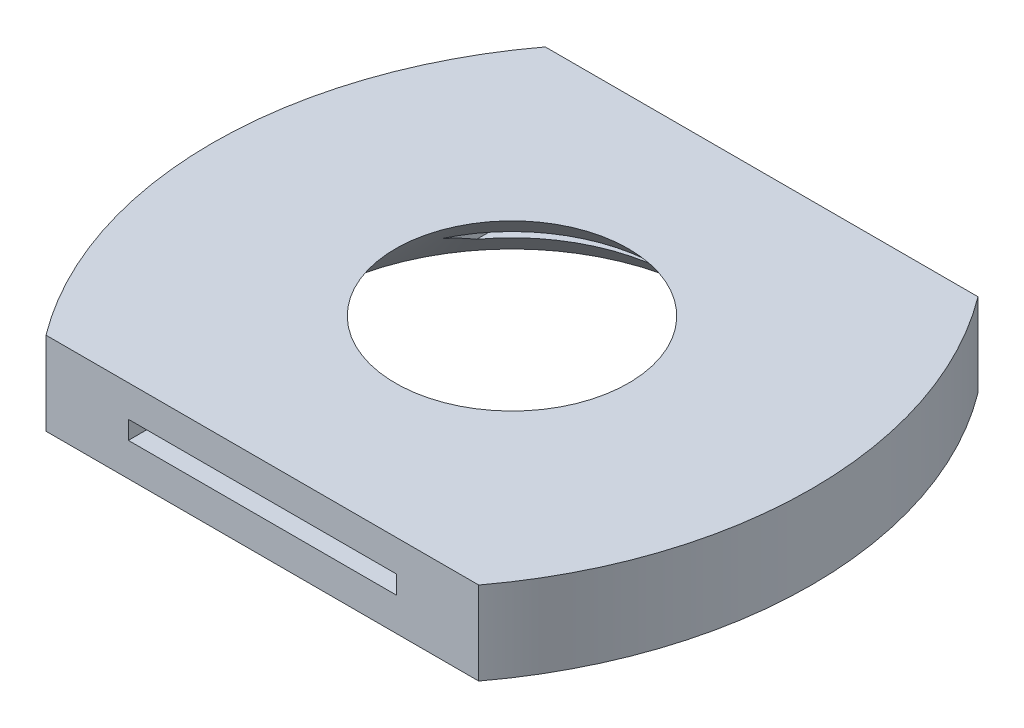
SolidWorks part; units mm, degrees
ref_plane "Front Plane" through (0, 0, 0) normal (0, 0, 1) x (1, 0, 0)
ref_plane "Top Plane" through (0, 0, 0) normal (0, 1, 0) x (1, 0, 0)
ref_plane "Right Plane" through (0, 0, 0) normal (1, 0, 0) x (0, 0, -1)
sketch "Lid case" plane through (0, 0, 0) normal (0, 1, 0) x (1, 0, 0)
  line L0 (-130, 150) -> (130, 150)
  line L1 (-130, -150) -> (130, -150)
  arc A0 (130, 150) -> (130, -150) centre (-70, 0) cw
  arc A1 (-130, 150) -> (-130, -150) centre (70, 0) ccw
  dimension "D6" = 250
  dimension "D7" = 250
  dimension "D1" = 260
  dimension "D2" = 130
  dimension "D3" = 150
  dimension "D4" = 150
  dimension "D5" = 130
extrude "Boss-Extrude1" add sketch "Lid case" along normal blind 50
ref_axis "Axis1" through (0, -54.3732, 0) along (0, 1, 0)
ref_plane "Plane1" through (0, 0, 0) normal (0, 0, 1) x (1, 0, 0)
sketch "Ventilation" plane through (0, 0, 0) normal (0, 0, 1) x (1, 0, 0)
  line L0 (0, 50) -> (0, 0)
  line L1 (0, 0) -> (-120, 0)
  line L2 (-120, 0) -> (-70, 50)
  line L4 (0, -54.3732) -> (0, 100.2697) construction
  line L5 (-130, 0) -> (130, 0) construction
  line L6 (-70, 50) -> (0, 50)
  line L7 (-130, 50) -> (130, 50) construction
  dimension "D2" = 120
  dimension "D3" = 45
revolve "Cut-Revolve1" cut sketch "Ventilation" angle 360 about axis through (0, -54.3732, 0) along (0, 1, 0)
sketch "Carbon filter hole" plane through (0, 0, 150) normal (0, 0, 1) x (1, 0, 0)
  line L0 (0, -54.3732) -> (0, 100.2697) construction
  line L1 (-80.5, 31) -> (80.5, 31)
  line L2 (-80.5, 31) -> (-80.5, 20)
  line L3 (-80.5, 20) -> (80.5, 20)
  line L4 (80.5, 31) -> (80.5, 20)
  line L6 (-130, 0) -> (130, 0) construction
  dimension "D1" = 161
  dimension "D2" = 11
  dimension "D3" = 80.5
  dimension "D4" = 20
extrude "Cut-Extrude3" cut sketch "Carbon filter hole" against normal blind 280
sketch "Sketch1" plane through (0, 0, 0) normal (0, -1, 0) x (1, 0, 0)
  line L0 (130, -150) -> (-130, -150) construction
  circle A0 centre (-110, -139) radius 3
  circle A1 centre (-82, -139) radius 3
  circle A2 centre (-54, -139) radius 3
  circle A3 centre (54, -139) radius 3
  circle A4 centre (82, -139) radius 3
  circle A5 centre (110, -139) radius 3
  point P16 (0, 0)
  dimension "D1" = 6
  dimension "D2" = 20
  dimension "D3" = 20
  dimension "D4" = 28
  dimension "D5" = 28
  dimension "D6" = 28
  dimension "D7" = 28
  dimension "D8" = 11
extrude "Cut-Extrude4" cut sketch "Sketch1" against normal blind 20
